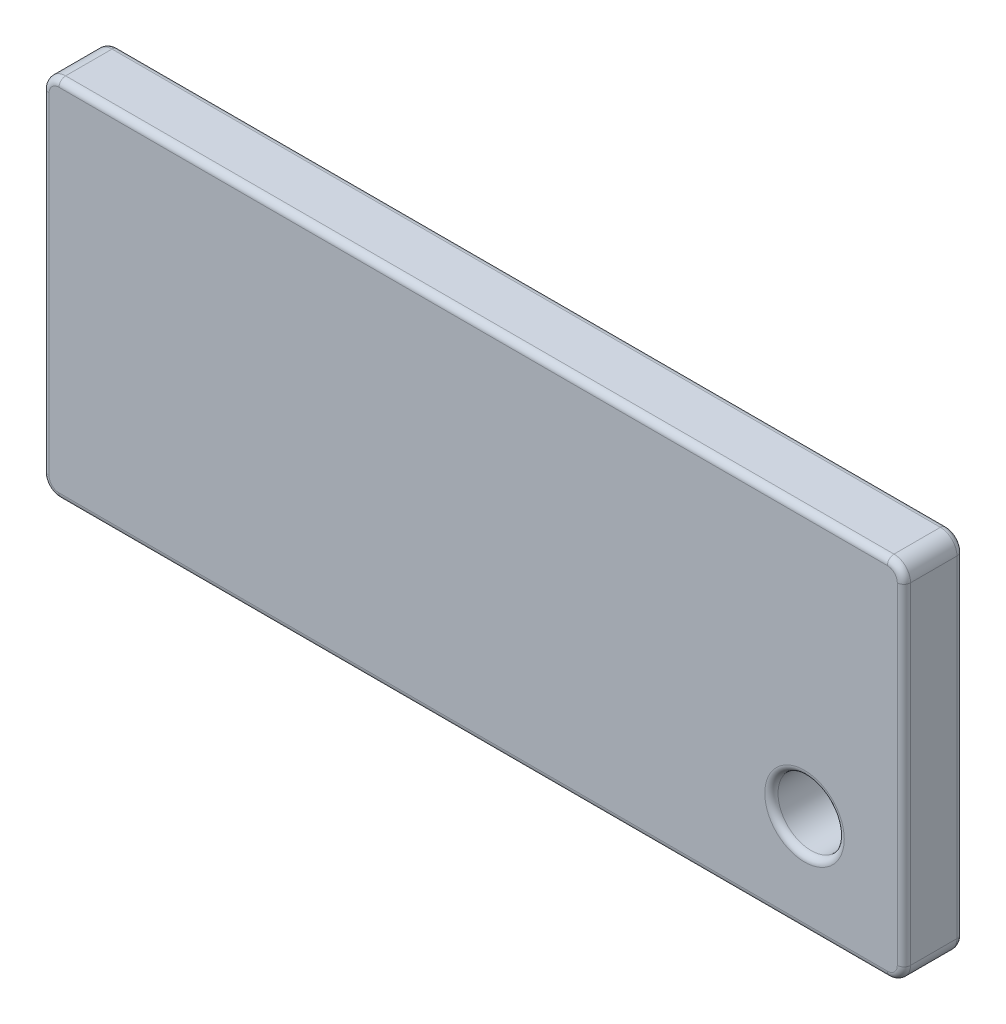
SolidWorks part; units mm, degrees
ref_plane "Front Plane" through (0, 0, 0) normal (0, 0, 1) x (1, 0, 0)
ref_plane "Top Plane" through (0, 0, 0) normal (0, 1, 0) x (1, 0, 0)
ref_plane "Right Plane" through (0, 0, 0) normal (1, 0, 0) x (0, 0, -1)
sketch "Sketch1" plane through (0, 0, 13.741) normal (0, 0, 1) x (1, 0, 0)
  line L0 (61.4432, -125.17) -> (87.4432, -125.17) construction
  line L1 (61.4432, -114.17) -> (61.4432, -125.17) construction
  line L2 (87.4432, -125.17) -> (87.4432, -114.17) construction
  line L3 (87.4432, -114.17) -> (61.4432, -114.17) construction
  line L4 (61.4432, -125.17) -> (87.4432, -125.17) construction
  line L5 (61.4432, -114.17) -> (61.4432, -125.17) construction
  line L6 (87.4432, -125.17) -> (87.4432, -114.17) construction
  line L7 (87.4432, -114.17) -> (61.4432, -114.17) construction
  line L8 (61.4432, -125.17) -> (87.4432, -125.17)
  line L9 (87.4432, -125.17) -> (87.4432, -114.17)
  line L10 (87.4432, -114.17) -> (61.4432, -114.17)
  line L11 (61.4432, -114.17) -> (61.4432, -125.17)
  dimension "D1" = 0
extrude "Boss-Extrude1" add sketch "Sketch1" against normal offset from surface (1.8 mm away) 0.2
fillet "Fillet1" radius 0.2 8 edges at (74.4432, -125.17, 11.941) (87.4432, -119.67, 11.941) (74.4432, -114.17, 11.941) (61.4432, -119.67, 11.941) (74.4432, -114.17, 13.741) (61.4432, -119.67, 13.741) (74.4432, -125.17, 13.741) (87.4432, -119.67, 13.741)
sketch "Sketch2" plane through (0, 0, 13.741) normal (0, 0, 1) x (1, 0, 0)
  line L0 (61.4432, -125.17) -> (87.4432, -125.17) construction
  line L1 (87.4432, -125.17) -> (87.4432, -114.17) construction
  circle A0 centre (84.4432, -122.17) radius 1
  dimension "D3" = 2
  dimension "D1" = 3
  dimension "D2" = 3
extrude "Cut-Extrude1" cut sketch "Sketch2" against normal through all
fillet "Fillet2" radius 0.5 12 edges at (87.3846, -125.1114, 11.9995) (87.3846, -114.2285, 11.9995) (61.5017, -114.2285, 11.9995) (61.5017, -125.1114, 11.9995) (61.4432, -125.17, 12.841) (61.4432, -114.17, 12.841) (87.4432, -114.17, 12.841) (87.4432, -125.17, 12.841) (87.3846, -125.1114, 13.6824) (87.3846, -114.2285, 13.6824) (61.5017, -114.2285, 13.6824) (61.5017, -125.1114, 13.6824)
fillet "Fillet3" radius 0.2 2 edges at (85.4432, -122.17, 11.941) (85.4432, -122.17, 13.741)
